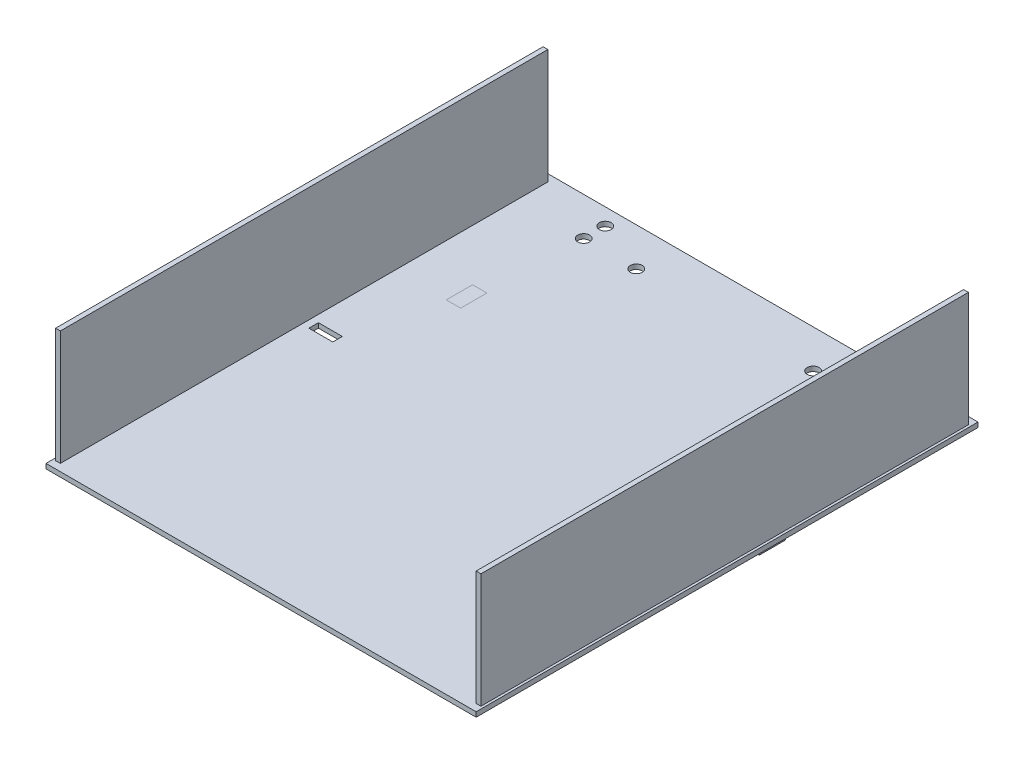
SolidWorks part; units mm, degrees
material "ABS"
ref_plane "Front Plane" through (0, 0, 0) normal (0, 0, 1) x (1, 0, 0)
ref_plane "Top Plane" through (0, 0, 0) normal (0, 1, 0) x (1, 0, 0)
ref_plane "Right Plane" through (0, 0, 0) normal (1, 0, 0) x (0, 0, -1)
sketch "Sketch1" plane through (0, 0, 0) normal (0, 1, 0) x (1, 0, 0)
  line L1 (90, 105) -> (-90, 105)
  line L2 (90, 105) -> (90, -105)
  line L3 (90, -105) -> (-90, -105)
  line L4 (-90, 105) -> (-90, -105)
  line L5 (90, 105) -> (-90, -105) construction
  line L6 (90, -105) -> (-90, 105) construction
  line L11 (84, 3) -> (74, 3)
  line L12 (84, 3) -> (84, -1)
  line L13 (84, -1) -> (74, -1)
  line L14 (74, 3) -> (74, -1)
  line L15 (84, 3) -> (74, -1) construction
  line L16 (84, -1) -> (74, 3) construction
  line L17 (-84, -1) -> (-74, -1)
  line L18 (-84, -1) -> (-84, 3)
  line L19 (-84, 3) -> (-74, 3)
  line L20 (-74, -1) -> (-74, 3)
  line L21 (-84, -1) -> (-74, 3) construction
  line L22 (-84, 3) -> (-74, -1) construction
  line L23 (-65.5, 38) -> (-59.5, 38)
  line L24 (-65.5, 38) -> (-65.5, 49)
  line L25 (-65.5, 49) -> (-59.5, 49)
  line L26 (-59.5, 38) -> (-59.5, 49)
  line L27 (-65.5, 38) -> (-59.5, 49) construction
  line L28 (-65.5, 49) -> (-59.5, 38) construction
  line L29 (59.5, 38) -> (65.5, 38)
  line L30 (59.5, 38) -> (59.5, 49)
  line L31 (59.5, 49) -> (65.5, 49)
  line L32 (65.5, 38) -> (65.5, 49)
  line L33 (59.5, 38) -> (65.5, 49) construction
  line L34 (59.5, 49) -> (65.5, 38) construction
  line L49 (-89, 102) -> (-87, 102)
  line L50 (-89, 102) -> (-89, -102)
  line L51 (-89, -102) -> (-87, -102)
  line L52 (-87, 102) -> (-87, -102)
  line L53 (89, 102) -> (87, 102)
  line L54 (89, 102) -> (89, -102)
  line L55 (89, -102) -> (87, -102)
  line L56 (87, 102) -> (87, -102)
  circle A0 centre (-59, 98) radius 2.5
  circle A1 centre (-59, 89) radius 2.5
  circle A2 centre (-37, 89) radius 2.5
  circle A3 centre (59, 98) radius 2.5
  circle A4 centre (59, 89) radius 2.5
  circle A5 centre (37, 89) radius 2.5
  point P0 (0, 0)
  point P6 (79, 1)
  point P23 (-79, 1)
  point P28 (-62.5, 43.5)
  point P33 (62.5, 43.5)
  point P40 (0, 0)
  dimension "D7" = 16
  dimension "D8" = 53
  dimension "D9" = 16
  dimension "D11" = 7
  dimension "D13" = 31
  dimension "D15" = 53
  dimension "D17" = 10
  dimension "D1" = 180
  dimension "D2" = 210
  dimension "D3" = 31
  dimension "D4" = 31
  dimension "D5" = 7
  dimension "D6" = 104
  dimension "D10" = 16
  dimension "D12" = 16
  dimension "D14" = 31
  dimension "D16" = 6
  dimension "D18" = 4
  dimension "D19" = 104
  dimension "D20" = 6
  dimension "D21" = 4
  dimension "D22" = 10
  dimension "D23" = 56
  dimension "D24" = 24.5
  dimension "D25" = 11
  dimension "D26" = 6
  dimension "D27" = 56
  dimension "D28" = 6
  dimension "D29" = 11
  dimension "D30" = 24.5
  dimension "D31" = 204
  dimension "D32" = 204
  dimension "D33" = 1
  dimension "D34" = 3
  dimension "D35" = 2
  dimension "D36" = 3
  dimension "D37" = 1
  dimension "D38" = 2
extrude "MainBody" add sketch "Sketch1" along normal blind 2
extrude "SayapRoda" add sketch "Sketch1<4>" against normal blind 25 and the other way blind 2 separate body contours L23 L26 L25 L24 | L29 L32 L31 L30 region at (-62.5, 0, -43.5) region at (62.5, 0, -43.5)
sketch "Sketch1<4>" plane through (0, 0, 0) normal (0, 1, 0) x (1, 0, 0) same geometry as "Sketch1"
hole_wizard "Hole1" positions "3DSketch2" profile "Sketch9" legacy end condition through all
sketch3d "3DSketch2"
  line L0 (65.5, 2, -49) -> (65.5, -25, -49) construction
  point P0 (65.5, -20.2331, -43.5)
  point P2 (65.5, -9.2332, -43.4453)
  point P4 (65.5, -7.7287, -43.5)
  point P6 (65.5, -6.2408, -43.5)
  point P8 (65.5, -4.8783, -43.5)
  point P13 (65.5, -7.7287, -43.5)
  point P14 (65.5, -6.2408, -43.5)
  point P15 (65.5, -4.8783, -43.5)
  point P16 (0, 0, 0)
  dimension "D1" = 11
  dimension "D2" = 5.5
  dimension "D3" = 5.5
  dimension "D4" = 5.5
  dimension "D5" = 5.5
sketch "Sketch9" plane through (65.5, -20.2331, -43.5) normal (0, 1, 0) x (0, 0, -1)
  line L0 (0, 0) -> (0, 155.5)
  line L1 (0, 155.5) -> (1.5, 155.5)
  line L2 (1.5, 155.5) -> (1.5, 0)
  line L3 (1.5, 0) -> (0, 0)
  line L4 (0, 110) -> (0, -10) construction
  dimension "Diameter" = 3
  dimension "Depth" = 155.5
extrude "Boss-Extrude4" add sketch "Sketch1<5>" along normal blind 50 contours L52 L49 L50 L51 | L53 L56 L55 L54 region at (-88, 0, 0) region at (88, 0, 0)
sketch "Sketch1<5>" plane through (0, 0, 0) normal (0, 1, 0) x (1, 0, 0) same geometry as "Sketch1"
